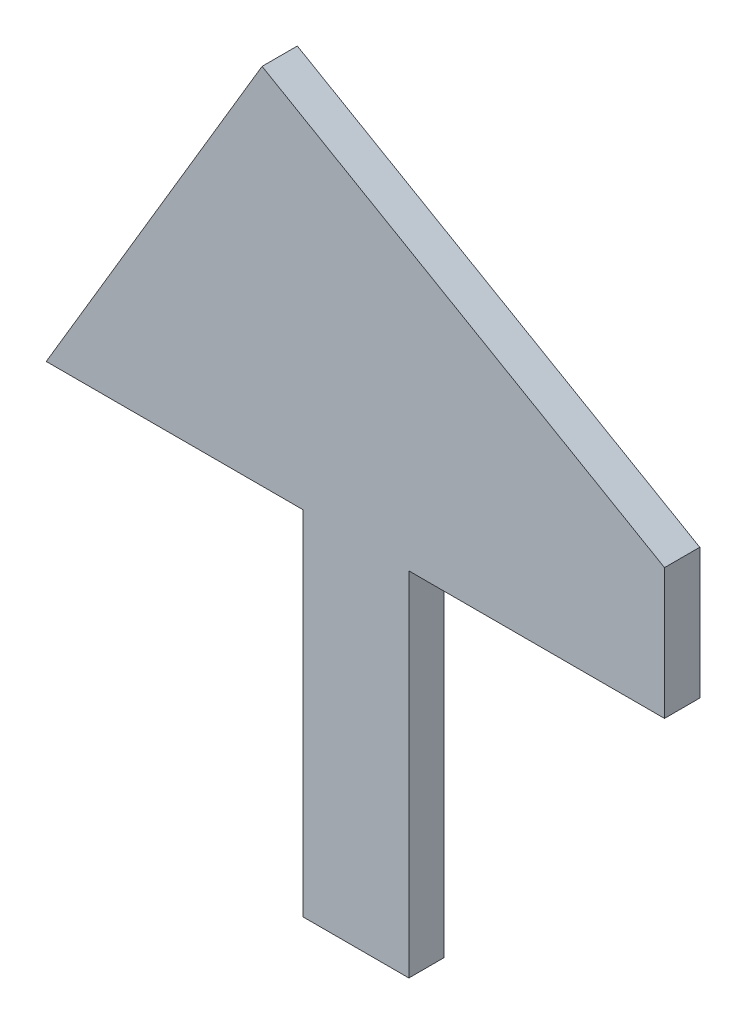
SolidWorks part; units mm, degrees
ref_plane "Front Plane" through (0, 0, 0) normal (0, 0, 1) x (1, 0, 0)
ref_plane "Top Plane" through (0, 0, 0) normal (0, 1, 0) x (1, 0, 0)
ref_plane "Right Plane" through (0, 0, 0) normal (1, 0, 0) x (0, 0, -1)
sketch "Sketch1" plane through (0, 0, 0) normal (0, 0, 1) x (1, 0, 0)
  line L2 (36.5, 3.7042) -> (36.5, 0)
  line L3 (36.5, 0) -> (29.25, 0)
  line L4 (17.9653, 0) -> (36.5, 0) construction
  line L7 (26.25, -10) -> (29.25, -10)
  line L8 (29.25, -10) -> (29.25, 0)
  line L9 (26.25, 0) -> (26.25, -10)
  line L10 (26.25, 0) -> (18.9653, 0)
  line L11 (18.9653, 0) -> (25.0865, 10.3091)
  line L12 (25.0865, 10.3091) -> (36.5, 3.7042)
  point P16 (24.2209, 10.81)
  dimension "D1" = 3
  dimension "D2" = 7.25
  dimension "D3" = 10
  dimension "D4" = 1
extrude "Boss-Extrude1" add sketch "Sketch1" along normal blind 1
